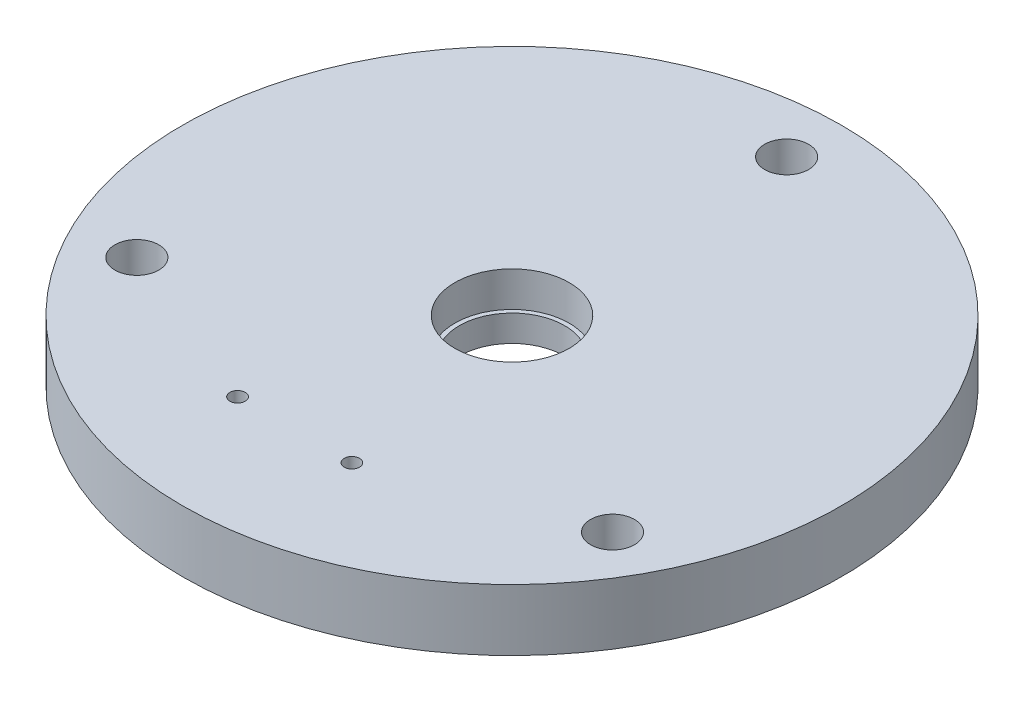
SolidWorks part; units mm, degrees
ref_plane "Front Plane" through (0, 0, 0) normal (0, 0, 1) x (1, 0, 0)
ref_plane "Top Plane" through (0, 0, 0) normal (0, 1, 0) x (1, 0, 0)
ref_plane "Right Plane" through (0, 0, 0) normal (1, 0, 0) x (0, 0, -1)
sketch "Sketch1" plane through (0, 0, 0) normal (0, 1, 0) x (1, 0, 0)
  circle A0 centre (0, 0) radius 75
  dimension "D1" = 150
extrude "Boss-Extrude1" add sketch "Sketch1" along normal blind 14
sketch "Sketch2" plane through (0, 14, 0) normal (0, 1, 0) x (1, 0, 0)
  circle A0 centre (0, 0) radius 13
  dimension "D1" = 26
extrude "Cut-Extrude1" cut sketch "Sketch2" against normal blind 8
sketch "Sketch3" plane through (0, 6, 0) normal (0, 1, 0) x (1, 0, 0)
  circle A0 centre (0, 0) radius 12
  dimension "D1" = 24
extrude "Cut-Extrude2" cut sketch "Sketch3" against normal blind 8
sketch "Sketch4" plane through (0, 14, 0) normal (0, 1, 0) x (1, 0, 0)
  line L0 (0, 0) -> (0, 62.5) construction
  line L1 (0, 0) -> (54.1266, -31.25) construction
  line L2 (0, 0) -> (-54.1266, -31.25) construction
  circle A0 centre (0, 62.5) radius 5
  circle A1 centre (-54.1266, -31.25) radius 5
  circle A2 centre (54.1266, -31.25) radius 5
  circle A3 centre (0, 0) radius 62.5
  dimension "D1" = 10
  dimension "D2" = 10
  dimension "D3" = 10
  dimension "D4" = 62.5
  dimension "D5" = 120
extrude "Cut-Extrude4" cut sketch "Sketch4" against normal through all contours A3 A0 | A0 A3 | A2 A3 | A3 A2 | A3 A1 | A1 A3 region at (0, 14, -64.5856) region at (0, 14, -60.3423) region at (-55.9328, 14, 32.2928) region at (-52.258, 14, 30.1712) region at (52.258, 14, 30.1712) region at (55.9328, 14, 32.2928)
cosmetic thread "Cosmetic Thread3" parameters "D2"=11
cosmetic thread "Cosmetic Thread4" parameters "D2"=11
cosmetic thread "Cosmetic Thread5" parameters "D2"=11
sketch "Sketch5" plane through (0, 14, 0) normal (0, 1, 0) x (1, 0, 0)
  line L0 (-33.2016, -67.2507) -> (-33.2016, -57.2507)
  line L1 (-33.2016, -57.2507) -> (28.7984, -57.2507)
  line L2 (-33.2016, -57.2507) -> (-33.2016, -22.2507)
  line L3 (-33.2016, -22.2507) -> (28.7984, -22.2507)
  line L4 (28.7984, -57.2507) -> (28.7984, -22.2507)
  line L5 (28.7984, -57.2507) -> (28.7984, -69.2507)
  circle A0 centre (0, 0) radius 75 construction
  circle A1 centre (-15.2016, -47.2507) radius 1.75
  circle A2 centre (10.7984, -47.2507) radius 1.75
  dimension "D9" = 3.5
  dimension "D10" = 3.5
  dimension "D1" = 35
  dimension "D2" = 62
  dimension "D3" = 10
  dimension "D4" = 12
  dimension "D5" = 10
  dimension "D6" = 10
  dimension "D7" = 18
  dimension "D8" = 18
extrude "Cut-Extrude5" cut sketch "Sketch5" against normal through all contours A1 | A2 region at (-15.2016, 14, 47.2507) region at (10.7984, 14, 47.2507)
cosmetic thread "Cosmetic Thread1" parameters "D2"=4
cosmetic thread "Cosmetic Thread2" parameters "D2"=4
